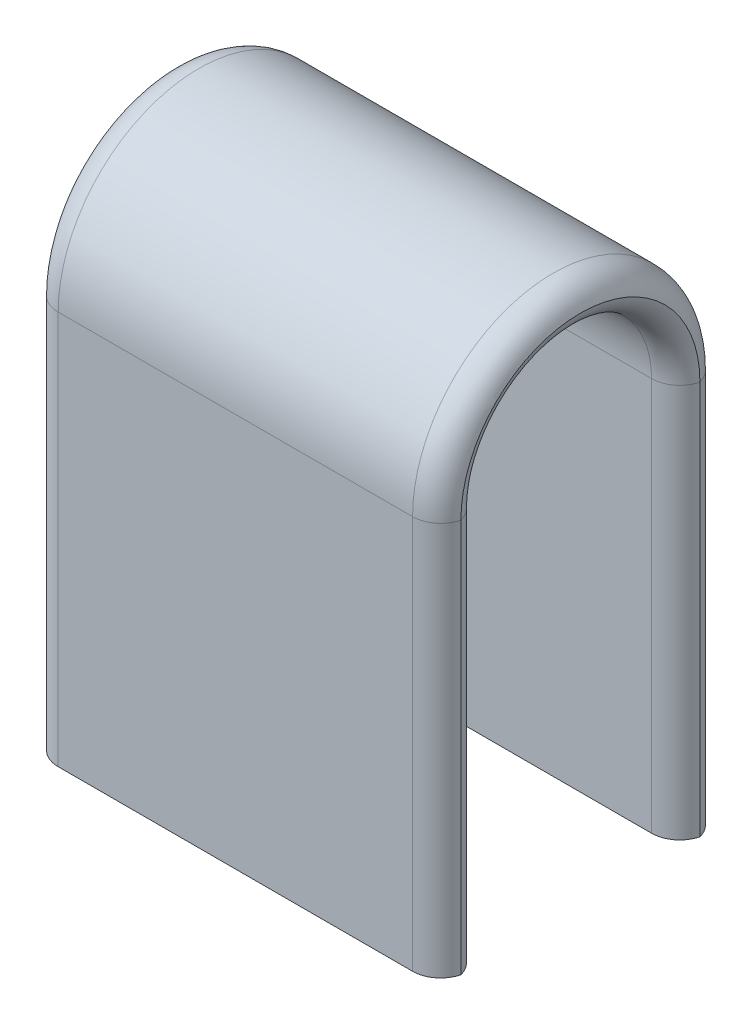
SolidWorks part; units mm, degrees
ref_plane "Front Plane" through (0, 0, 0) normal (0, 0, 1) x (1, 0, 0)
ref_plane "Top Plane" through (0, 0, 0) normal (0, 1, 0) x (1, 0, 0)
ref_plane "Right Plane" through (0, 0, 0) normal (1, 0, 0) x (0, 0, -1)
sketch "Sketch1" plane through (0, 0, 0) normal (0, 0, 1) x (1, 0, 0)
  line L1 (-9.271, -8.89) -> (9.271, -8.89)
  line L2 (-9.271, -8.89) -> (-9.271, 8.89)
  line L3 (-9.271, 8.89) -> (9.271, 8.89)
  line L4 (9.271, -8.89) -> (9.271, 8.89)
  line L5 (-9.271, -8.89) -> (9.271, 8.89) construction
  line L6 (-9.271, 8.89) -> (9.271, -8.89) construction
  point P0 (0, 0)
  dimension "D1" = 17.78
  dimension "D2" = 18.542
ref_plane "Plane2" through (0, 0, -12.7) normal (0, 0, 1) x (1, 0, 0)
sketch "Sketch4" plane through (0, 0, -12.7) normal (0, 0, 1) x (1, 0, 0)
  line L1 (9.271, -8.89) -> (-9.271, -8.89)
  line L2 (9.271, -8.89) -> (9.271, 8.89)
  line L3 (9.271, 8.89) -> (-9.271, 8.89)
  line L4 (-9.271, -8.89) -> (-9.271, 8.89)
  line L5 (9.271, -8.89) -> (-9.271, 8.89) construction
  line L6 (9.271, 8.89) -> (-9.271, -8.89) construction
  point P0 (0, 0)
extrude "Boss-Extrude4" add sketch "Sketch1" against normal blind 1.905
extrude "Boss-Extrude5" add sketch "Sketch4" along normal blind 1.905 separate body
ref_plane "Plane3" through (0, 0, -6.35) normal (0, 0, 1) x (1, 0, 0)
ref_plane "Plane4" through (0, 8.89, 0) normal (0, 1, 0) x (1, 0, 0)
ref_plane "Plane5" through (-9.271, 0, 0) normal (-1, 0, 0) x (0, 0, 1)
sketch "Sketch6" plane through (-9.271, 0, 0) normal (-1, 0, 0) x (0, 0, 1)
  line L0 (-12.7, 0) -> (0, 0) construction
  line L1 (-12.7, -5.4994) -> (-12.7, 5.4994) construction
  line L2 (-1.905, 8.89) -> (-1.905, -8.89) construction
  line L3 (10.1981, 8.89) -> (-10.1981, 8.89) construction
  line L4 (-6.35, 8.89) -> (-6.35, 7.62) construction
  line L5 (-10.795, 8.89) -> (-12.7, 8.89) construction
  line L6 (-12.7, 8.89) -> (-10.795, 8.89)
  line L7 (-1.905, 8.89) -> (0, 8.89)
  arc A0 (-10.795, 8.89) -> (-1.905, 8.89) centre (-6.35, 8.89) cw
  arc A1 (0, 8.89) -> (-12.7, 8.89) centre (-6.35, 8.89) ccw
extrude "Boss-Extrude6" add sketch "Sketch6" against normal up to surface (18.542 mm away) up to face at (9.271, 0, -0.9525)
fillet "Fillet1" radius 1.27 12 edges at (-9.271, 13.335, -6.35) (-9.271, 15.24, -6.35) (9.271, 13.335, -6.35) (9.271, 15.24, -6.35) (-9.271, 0, -12.7) (-9.271, 0, -10.795) (-9.271, 0, -1.905) (-9.271, 0, 0) (9.271, 0, 0) (9.271, 0, -1.905) (9.271, 0, -10.795) (9.271, 0, -12.7)
